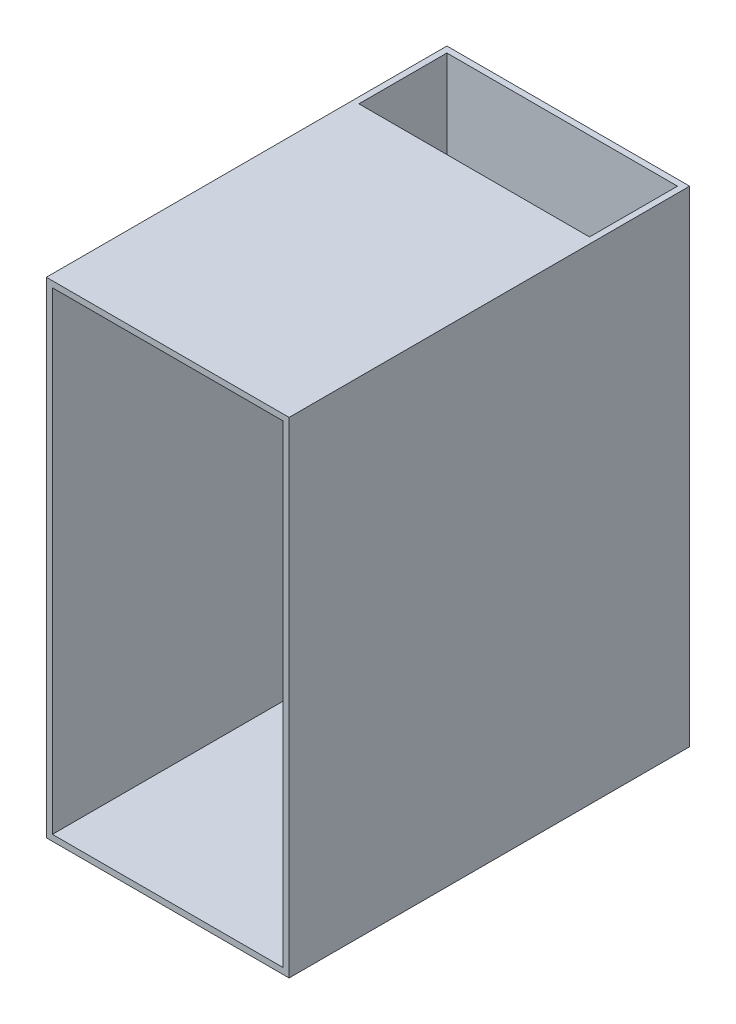
SolidWorks part; units mm, degrees
ref_plane "Front Plane" through (0, 0, 0) normal (0, 0, 1) x (1, 0, 0)
ref_plane "Top Plane" through (0, 0, 0) normal (0, 1, 0) x (1, 0, 0)
ref_plane "Right Plane" through (0, 0, 0) normal (1, 0, 0) x (0, 0, -1)
sketch "Sketch1" plane through (0, 0, 0) normal (0, 0, 1) x (1, 0, 0)
  line L1 (-40, 80) -> (40, 80)
  line L2 (-40, 80) -> (-40, -80)
  line L3 (-40, -80) -> (40, -80)
  line L4 (40, 80) -> (40, -80)
  line L5 (-40, 80) -> (40, -80) construction
  line L6 (-40, -80) -> (40, 80) construction
  point P0 (0, 0)
  dimension "D1" = 80
  dimension "D2" = 160
extrude "Boss-Extrude1" add sketch "Sketch1" along normal blind 2
sketch "Sketch2" plane through (0, 0, 2) normal (0, 0, 1) x (1, 0, 0)
  line L1 (-40, 80) -> (40, 80)
  line L2 (-40, 80) -> (-40, -80)
  line L3 (-40, -80) -> (40, -80)
  line L4 (40, 80) -> (40, -80)
  line L5 (-40, 80) -> (40, -80) construction
  line L6 (-40, -80) -> (40, 80) construction
  line L7 (-38, 78) -> (38, 78)
  line L8 (-38, 78) -> (-38, -78)
  line L9 (-38, -78) -> (38, -78)
  line L10 (38, 78) -> (38, -78)
  line L11 (-38, 78) -> (38, -78) construction
  line L12 (-38, -78) -> (38, 78) construction
  point P0 (0, 0)
  point P7 (0, 0)
  dimension "D1" = 2
  dimension "D2" = 2
extrude "Boss-Extrude2" add sketch "Sketch2" along normal blind 130
sketch "Sketch3" plane through (0, -80, 0) normal (0, -1, 0) x (1, 0, 0)
  line L0 (0, 0) -> (0, 39.4708) construction
  line L2 (-31, 20) -> (31, 20)
  line L3 (-31, 20) -> (-31, 2)
  line L4 (-31, 2) -> (31, 2)
  line L5 (31, 20) -> (31, 2)
  line L6 (-40, 0) -> (40, 0) construction
  dimension "D1" = 62
  dimension "D2" = 31
  dimension "D3" = 18
  dimension "D4" = 2
extrude "Cut-Extrude1" cut sketch "Sketch3" against normal blind 2
sketch "Sketch5" plane through (0, 80, 0) normal (0, 1, 0) x (1, 0, 0)
  line L0 (0, 0) -> (0, -35.9841) construction
  line L2 (40, 0) -> (-40, 0) construction
  line L7 (40, -132) -> (40, 0) construction
  line L8 (-38, -2) -> (38, -2)
  line L9 (-38, -2) -> (-38, -31)
  line L10 (-38, -31) -> (38, -31)
  line L11 (38, -2) -> (38, -31)
  line L12 (-40, -132) -> (-40, 0) construction
  dimension "D1" = 2
  dimension "D2" = 2
  dimension "D3" = 2
  dimension "D4" = 29
extrude "Cut-Extrude2" cut sketch "Sketch5" against normal blind 2
sketch "Sketch7" plane through (0, -78, 0) normal (0, 1, 0) x (1, 0, 0)
  line L0 (38, -132) -> (38, -2) construction
  line L1 (-38, -20) -> (38, -20)
  line L2 (-38, -20) -> (-38, -30)
  line L3 (-38, -30) -> (38, -30)
  line L4 (38, -20) -> (38, -30)
  line L5 (-38, -132) -> (-38, -2) construction
  line L6 (31, -20) -> (-31, -20) construction
  dimension "D1" = 0
  dimension "D2" = 0
  dimension "D3" = 0
  dimension "D4" = 10
extrude "Boss-Extrude3" add sketch "Sketch7" along normal blind 20
chamfer "Chamfer1" distance 17 angle 45 1 edges at (0, -58, 30)
fillet "Fillet1" radius 10 1 edges at (0, -75, 30)
